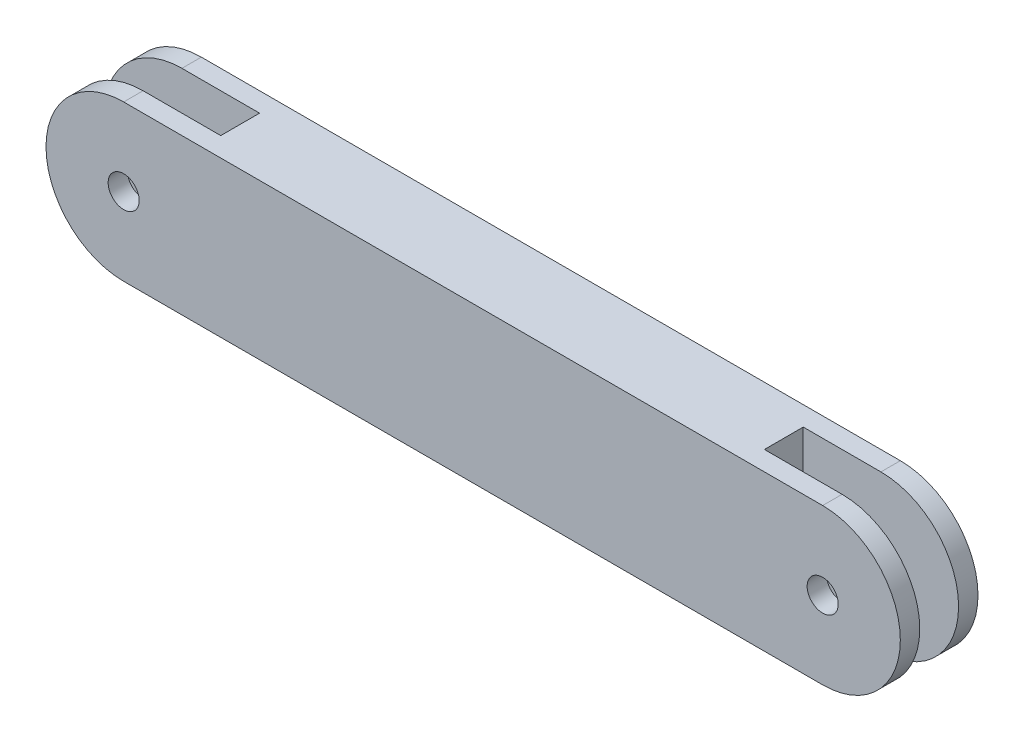
SolidWorks part; units mm, degrees
ref_plane "Plan de face" through (0, 0, 0) normal (0, 0, 1) x (1, 0, 0)
ref_plane "Plan de dessus" through (0, 0, 0) normal (0, 1, 0) x (1, 0, 0)
ref_plane "Plan de droite" through (0, 0, 0) normal (1, 0, 0) x (0, 0, -1)
sketch "Esquisse1" plane through (0, 0, 0) normal (0, 0, 1) x (1, 0, 0)
  line L19 (0, 0) -> (180, 0) construction
  line L20 (0, 20) -> (180, 20)
  line L21 (0, -20) -> (180, -20)
  arc A0 (0, 20) -> (0, -20) centre (0, 0) ccw
  arc A1 (180, -20) -> (180, 20) centre (180, 0) ccw
  circle A2 centre (0, 0) radius 4
  circle A3 centre (180, 0) radius 4
  point P3 (90, 0)
  dimension "D1" = 20
  dimension "D2" = 180
  dimension "D3" = 8
extrude "Boss.-Extru.1" add sketch "Esquisse1" along normal blind 20
sketch "Esquisse2" plane through (0, 0, 0) normal (1, 0, 0) x (0, 0, -1)
  line L0 (-20, 20) -> (0, 20) construction
  line L1 (-15, 20) -> (-5, 20)
  line L2 (-15, 20) -> (-15, -20)
  line L3 (-15, -20) -> (-5, -20)
  line L4 (-5, 20) -> (-5, -20)
  line L5 (-20, -20) -> (0, -20) construction
  point P8 (-10, 20)
  point P9 (-10, 20)
  dimension "D1" = 10
extrude "Enlèv. mat.-Extru.1" cut sketch "Esquisse2" against normal blind 20 and the other way blind 20
ref_plane "Plan1" through (90, 0, 0) normal (1, 0, 0) x (0, 0, -1)
mirror "Symétrie1" about plane through (90, 0, 0) normal (1, 0, 0) of "Enlèv. mat.-Extru.1"
